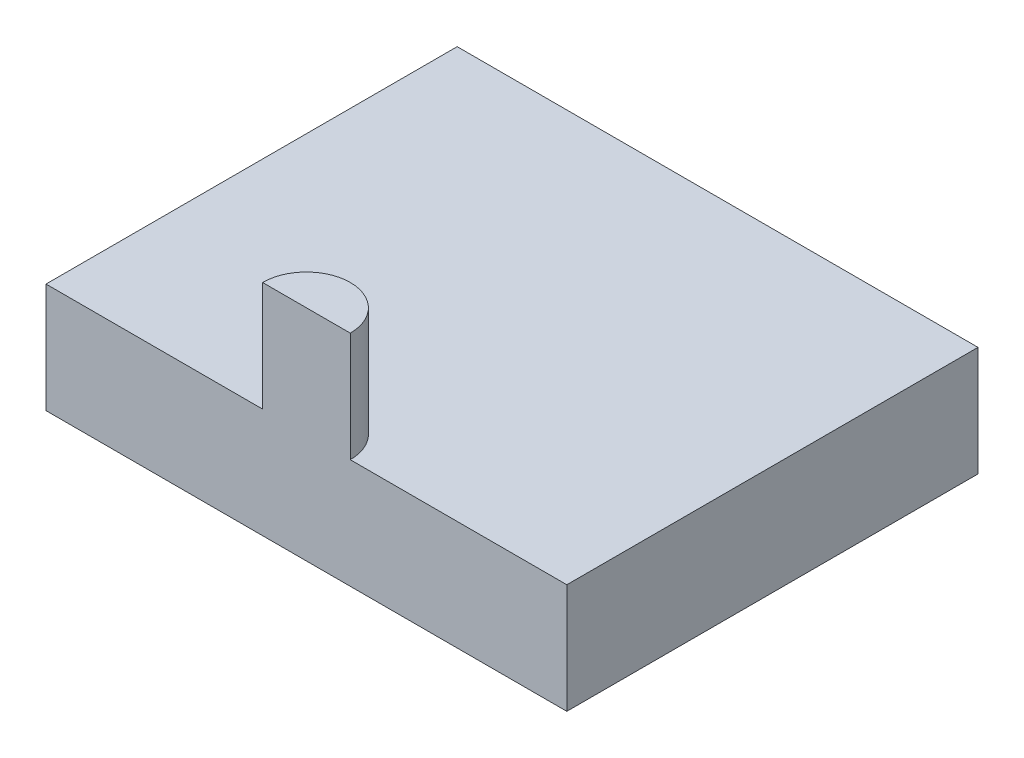
SolidWorks part; units mm, degrees
ref_plane "Front Plane" through (0, 0, 0) normal (0, 0, 1) x (1, 0, 0)
ref_plane "Top Plane" through (0, 0, 0) normal (0, 1, 0) x (1, 0, 0)
ref_plane "Right Plane" through (0, 0, 0) normal (1, 0, 0) x (0, 0, -1)
sketch "Sketch1" plane through (0, 0, 0) normal (0, 1, 0) x (1, 0, 0)
  line L1 (-47.5, 37.5) -> (47.5, 37.5)
  line L2 (-47.5, 37.5) -> (-47.5, -37.5)
  line L3 (-47.5, -37.5) -> (47.5, -37.5)
  line L4 (47.5, 37.5) -> (47.5, -37.5)
  line L5 (-47.5, 37.5) -> (47.5, -37.5) construction
  line L6 (-47.5, -37.5) -> (47.5, 37.5) construction
  point P0 (0, 0)
  dimension "D1" = 95
  dimension "D2" = 75
extrude "Boss-Extrude1" add sketch "Sketch1" along normal mid plane 20
sketch "Sketch2" plane through (0, 0, 37.5) normal (0, 0, 1) x (1, 0, 0)
  line L0 (0, 10) -> (0, 30)
  line L1 (-47.5, 10) -> (47.5, 10) construction
  line L2 (0, 30) -> (-8, 30)
  line L3 (-8, 30) -> (-8, 10)
  line L4 (-8, 10) -> (0, 10)
  dimension "D1" = 8
  dimension "D2" = 20
revolve "Revolve1" add sketch "Sketch2" angle 180 about L0 reverse direction yes
